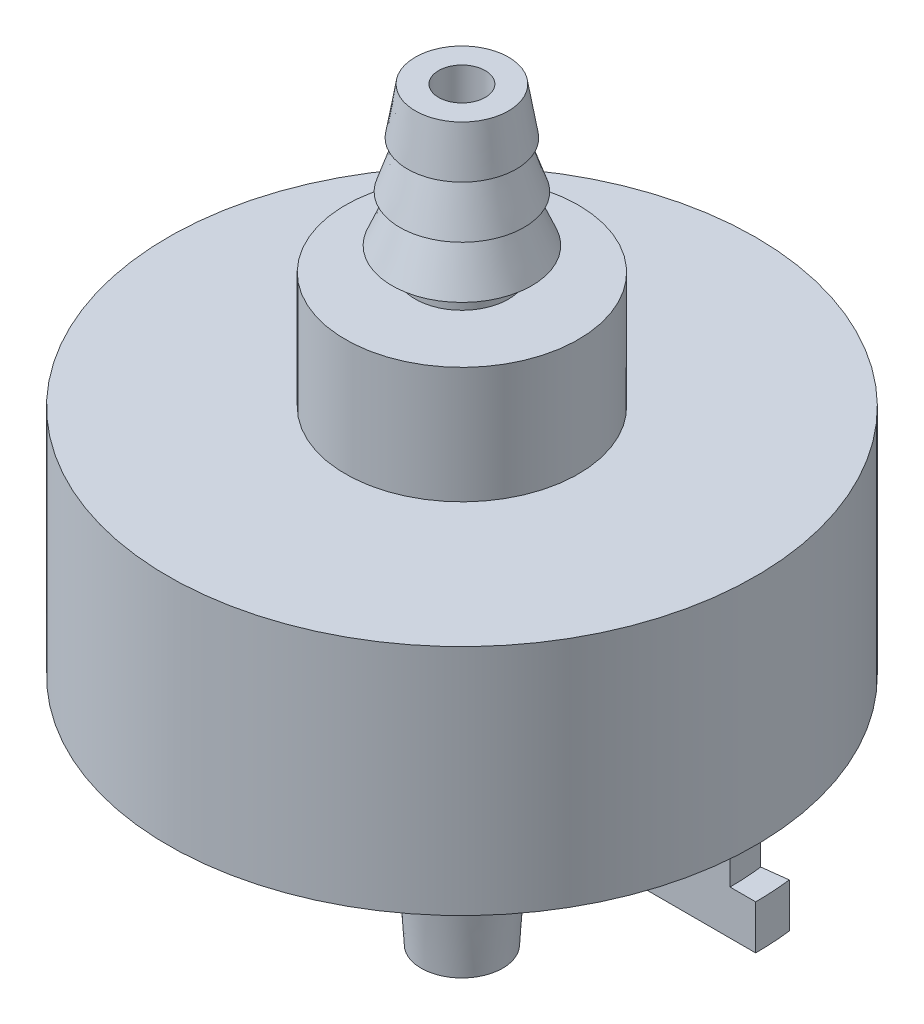
SolidWorks part; units mm, degrees
ref_plane "Front Plane" through (0, 0, 0) normal (0, 0, 1) x (1, 0, 0)
ref_plane "Top Plane" through (0, 0, 0) normal (0, 1, 0) x (1, 0, 0)
ref_plane "Right Plane" through (0, 0, 0) normal (1, 0, 0) x (0, 0, -1)
sketch "Sketch5" plane through (0, 0, 0) normal (0, 0, 1) x (1, 0, 0)
  line L0 (8.9789, 5) -> (-4.2566, 5) construction
  line L1 (0, 0) -> (17.9578, 0) construction
  line L2 (17.9578, 0) -> (0, 0) construction
  line L3 (8.9789, 0) -> (8.9789, 13.104) construction
  line L4 (6.9789, 0) -> (6.9789, 13) construction
  line L5 (7.9789, 0) -> (9.9789, 0) construction
  line L6 (7.9789, 0) -> (7.9789, 12)
  line L7 (7.9789, 12) -> (9.9789, 12) construction
  line L8 (9.9789, 0) -> (9.9789, 12) construction
  line L9 (6.9789, 13) -> (10.9789, 13) construction
  line L10 (10.9789, 0) -> (10.9789, 13) construction
  line L11 (7.9789, 12) -> (6.9789, 12)
  line L12 (8.9789, 10) -> (6.9789, 10) construction
  line L13 (8.9789, 8) -> (6.9789, 8) construction
  line L14 (8.9789, 6) -> (5.9789, 6) construction
  line L15 (6.9789, 12) -> (5.9789, 6) construction
  line L16 (6.9789, 5) -> (6.9789, 6)
  line L17 (7.9789, 0) -> (0, 0) construction
  line L18 (6.9789, 6) -> (5.9789, 6)
  line L19 (6.9789, 8) -> (6.3122, 8) construction
  line L20 (6.9789, 10) -> (6.6456, 10)
  line L21 (6.9789, 10) -> (6.3122, 8)
  line L22 (6.9789, 12) -> (6.6456, 10)
  line L23 (6.3122, 8) -> (6.8122, 8)
  line L24 (5.9789, 6) -> (6.8122, 8)
  line L25 (6.9789, 5) -> (3.9789, 5)
  line L26 (3.9789, 5) -> (3.9789, 0)
  line L27 (7.9789, 0) -> (3.9789, 0)
  arc A0 (0, 0) -> (6.9789, 5) centre (-2.0494, 10.231) ccw construction
  dimension "D1" = 5
  dimension "D2" = 2
  dimension "D3" = 1
  dimension "D4" = 12
  dimension "D5" = 2
  dimension "D6" = 2
  dimension "D7" = 2
  dimension "D8" = 3
  dimension "D9" = 0.5
  dimension "D10" = 5
revolve "Revolve3" add sketch "Sketch5" angle 360 about L3
sketch "Sketch6" plane through (0, 0, 0) normal (0, -1, 0) x (1, 0, 0)
  circle A0 centre (8.9789, 0) radius 1
  circle A1 centre (8.9789, 0) radius 12.61
  dimension "D1" = 25.22
extrude "Boss-Extrude2" add sketch "Sketch6" along normal blind 10
sketch "Sketch7" plane through (0, 0, 0) normal (0, 0, 1) x (1, 0, 0)
  line L0 (-3.6311, -10) -> (21.5889, -10) construction
  line L1 (-3.6311, -10) -> (1.1689, -10) construction
  line L2 (-3.6311, -10) -> (-3.6311, -14) construction
  line L3 (-3.6311, -14) -> (1.1689, -14)
  line L4 (1.1689, -10) -> (1.1689, -14) construction
  line L5 (-2.5311, -10) -> (0.0689, -10)
  line L6 (-3.6311, -10) -> (-2.5311, -10) construction
  line L7 (-3.6311, -10) -> (-3.6311, -12.1) construction
  line L8 (-3.6311, -12.1) -> (-2.5311, -12.1)
  line L9 (-2.5311, -10) -> (-2.5311, -12.1)
  line L10 (1.1689, -10) -> (0.0689, -10) construction
  line L11 (1.1689, -10) -> (1.1689, -12.1) construction
  line L12 (1.1689, -12.1) -> (0.0689, -12.1)
  line L13 (0.0689, -10) -> (0.0689, -12.1)
  line L14 (1.1689, -12.1) -> (1.1689, -14)
  line L15 (-3.6311, -12.1) -> (-3.6311, -14)
  point P6 (-3.6311, -10)
  dimension "D1" = 4.8
  dimension "D2" = 4
  dimension "D3" = 1.1
  dimension "D4" = 1.1
  dimension "D5" = 1.9
  dimension "D6" = 1.9
ref_axis "Axis1" through (8.9789, -10, 0) along (0, 1, 0)
revolve "Revolve4" add sketch "Sketch7" angle 7 about axis through (8.9789, -10, 0) along (0, 1, 0)
pattern_circular "CirPattern1" count 2 over 360 about axis through (8.9789, -10, 0) along (0, 1, 0) of "Revolve4"
sketch "Sketch8" plane through (0, -10, 0) normal (0, -1, 0) x (1, 0, 0)
  circle A0 centre (8.9789, 0) radius 1
  circle A1 centre (8.9789, 0) radius 2.75
  dimension "D1" = 5.5
ref_plane "Plane1" through (0, -20, 0) normal (0, -1, 0) x (-1, 0, 0)
sketch "Sketch9" plane through (0, -20, 0) normal (0, -1, 0) x (-1, 0, 0)
  circle A0 centre (-8.9789, 0) radius 1
  circle A1 centre (-8.9789, 0) radius 1.75
  circle A2 centre (-8.9789, 0) radius 2.75 construction
  dimension "D1" = 1
loft "Loft1" add section "Sketch8" section "Sketch9" start constraint default connector at (6.9002, -10, -1.8004) connector at (8.5108, -20, -1.6862)
hole_wizard "Ø2.0 (2) Diameter Hole1" positions "Sketch10" profile "Sketch11" hole size "Ø2.0" standard "ANSI Metric" end condition through all
sketch "Sketch10" plane through (0, -20, 0) normal (0, -1, 0) x (-1, 0, 0)
  point P0 (-8.9789, 0)
sketch "Sketch11" plane through (8.9789, -20, 0) normal (1, 0, 0) x (0, 0, -1)
  line L0 (0, 0) -> (0, 32)
  line L1 (0, 32) -> (1, 32)
  line L2 (1, 32) -> (1, 0)
  line L5 (1, 0) -> (0, 0)
  line L11 (0, -6.35) -> (0, 107.95) construction
  dimension "Thru Hole Dia." = 2
  dimension "Thru Hole Depth" = 32
